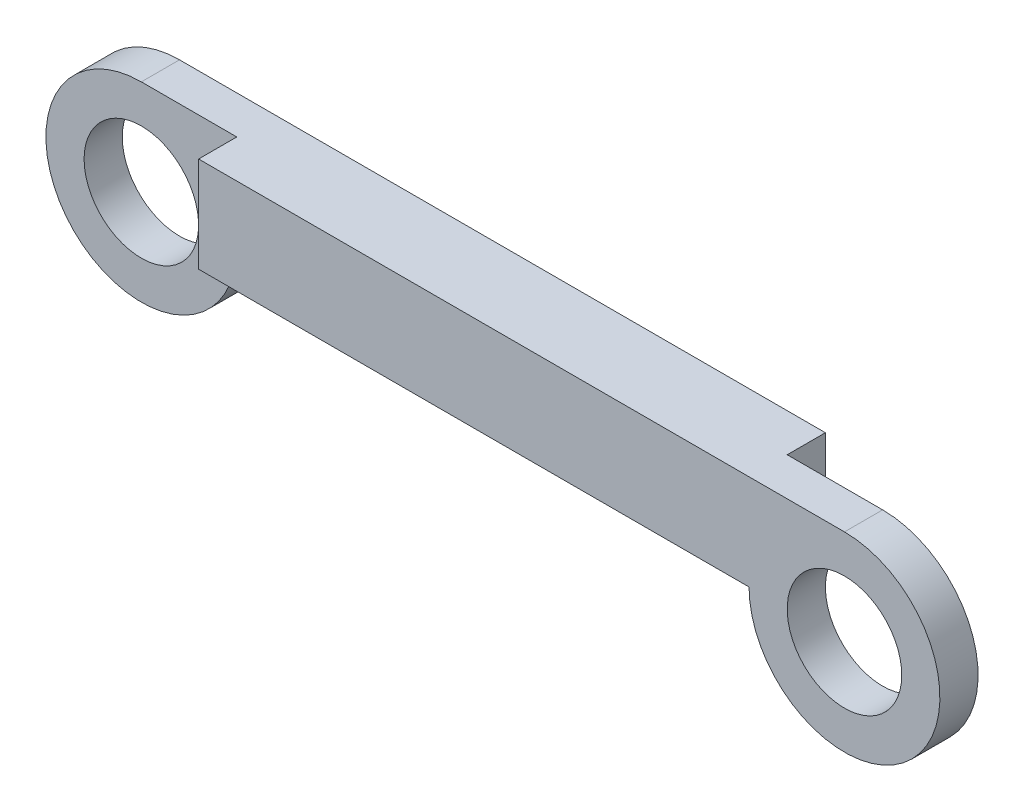
SolidWorks part; units mm, degrees
ref_plane "Front" through (0, 0, 0) normal (0, 0, 1) x (1, 0, 0)
ref_plane "Top" through (0, 0, 0) normal (0, 1, 0) x (1, 0, 0)
ref_plane "Right" through (0, 0, 0) normal (1, 0, 0) x (0, 0, -1)
sketch "Sketch1" plane through (0, 0, 0) normal (0, 0, 1) x (1, 0, 0)
  line L0 (-72.1, -25) -> (72.1, -25)
  line L1 (-97.1, 0) -> (97.1, 0)
  circle A0 centre (-97.1, -25) radius 15
  arc A1 (-97.1, 0) -> (-72.1, -25) centre (-97.1, -25) ccw
  arc A2 (72.1, -25) -> (97.1, 0) centre (97.1, -25) ccw
  circle A3 centre (97.1, -25) radius 15
  dimension "D1" = 50
  dimension "D2" = 30
  dimension "D3" = 30
  dimension "D4" = 194.2
extrude "Boss-Extrude1" add sketch "Sketch1" along normal blind 20
sketch "Sketch2" plane through (0, 0, 0) normal (0, 1, 0) x (1, 0, 0)
  line L8 (72.1, 0) -> (122.1, 0)
  line L9 (72.1, 0) -> (72.1, -10)
  line L10 (-122.1, -10) -> (-72.1, -10)
  line L11 (-122.1, -20) -> (-72.1, -20)
  line L12 (-122.1, -20) -> (-122.1, -10)
  line L13 (72.1, -10) -> (122.1, -10)
  line L14 (-72.1, -20) -> (-72.1, -10)
  line L15 (122.1, 0) -> (122.1, -10)
extrude "Cut-Extrude1" cut sketch "Sketch2" against normal blind 84
